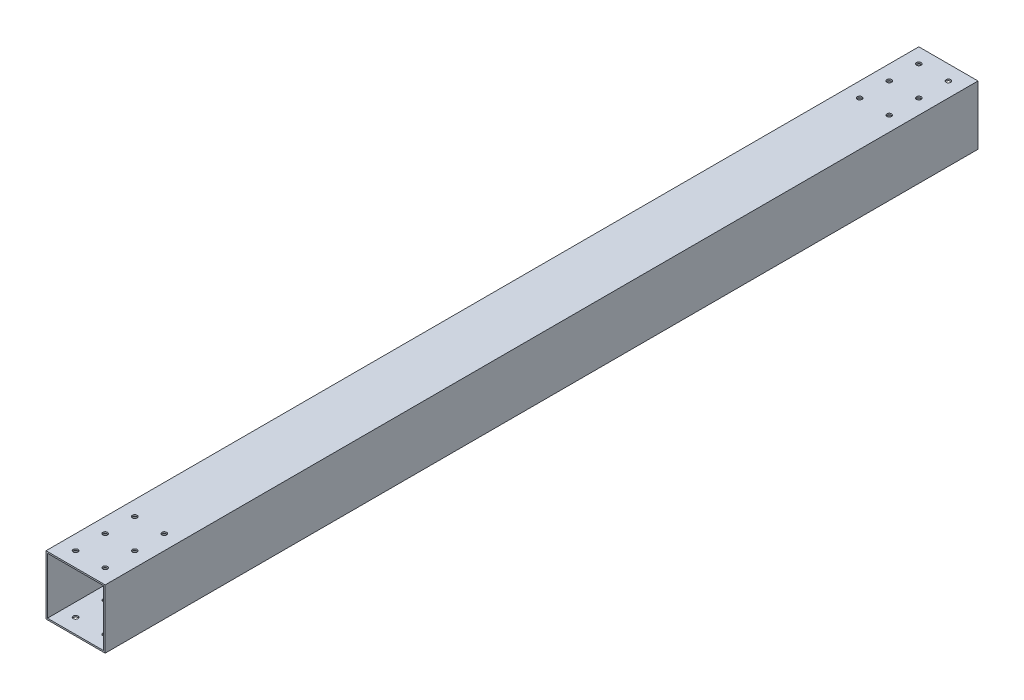
SolidWorks part; units mm, degrees
material "6061 合金"
ref_plane "前视基准面" through (0, 0, 0) normal (0, 0, 1) x (1, 0, 0)
ref_plane "上视基准面" through (0, 0, 0) normal (0, 1, 0) x (1, 0, 0)
ref_plane "右视基准面" through (0, 0, 0) normal (1, 0, 0) x (0, 0, -1)
other "Configuration Table"
sketch "草图1" plane through (0, 0, 0) normal (0, 0, 1) x (1, 0, 0)
  line L1 (-20, 20) -> (20, 20)
  line L2 (-20, 20) -> (-20, -20)
  line L3 (-20, -20) -> (20, -20)
  line L4 (20, 20) -> (20, -20)
  line L5 (-20, 20) -> (20, -20) construction
  line L6 (-20, -20) -> (20, 20) construction
  line L7 (-19, 19) -> (19, 19)
  line L8 (-19, 19) -> (-19, -19)
  line L9 (-19, -19) -> (19, -19)
  line L10 (19, 19) -> (19, -19)
  line L11 (-19, 19) -> (19, -19) construction
  line L12 (-19, -19) -> (19, 19) construction
  point P0 (0, 0)
  point P6 (0, 0)
  dimension "D1" = 40
  dimension "D2" = 1
extrude "凸台-拉伸1" add sketch "草图1" along normal mid plane 590
sketch "草图2" plane through (0, 20, 0) normal (0, 1, 0) x (1, 0, 0)
  line L0 (0, -290) -> (0, -50290) construction
  line L1 (20, -295) -> (-20, -295) construction
  line L2 (-10, -285) -> (-10, -265) construction
  line L3 (0, 0) -> (50000, 0) construction
  circle A0 centre (-10, -285) radius 1.6
  circle A1 centre (10, -285) radius 1.6
  circle A2 centre (-10, -265) radius 1.6
  circle A3 centre (10, -265) radius 1.6
  circle A4 centre (-10, -245) radius 1.6
  circle A5 centre (10, -245) radius 1.6
  circle A10 centre (10, 245) radius 1.6
  circle A11 centre (-10, 245) radius 1.6
  circle A12 centre (10, 265) radius 1.6
  circle A13 centre (-10, 265) radius 1.6
  circle A14 centre (10, 285) radius 1.6
  circle A15 centre (-10, 285) radius 1.6
  circle A16 centre (10, -225) radius 1.6 [skipped]
  circle A17 centre (-10, -225) radius 1.6 [skipped]
  point P4 (0, -295)
  dimension "D1" = 20
  dimension "D2" = 3.2
  dimension "D3" = 10
  dimension "D5" = 20
  dimension "D4" = 4
extrude "切除-拉伸1" cut sketch "草图2" against normal through all
sketch "草图3" plane through (-20, 0, 0) normal (-1, 0, 0) x (0, 0, 1)
  line L0 (-215, 10) -> (-200, 10) construction
  line L1 (-215, 17) -> (-200, 17)
  line L2 (-215, 3) -> (-200, 3)
  line L3 (295, 20) -> (-295, 20) construction
  line L4 (-295, 20) -> (-295, -20) construction
  line L5 (-95, 10) -> (-80, 10) construction
  line L6 (-95, 17) -> (-80, 17)
  line L7 (-95, 3) -> (-80, 3)
  arc A0 (-215, 17) -> (-215, 3) centre (-215, 10) ccw
  arc A1 (-200, 3) -> (-200, 17) centre (-200, 10) ccw
  arc A2 (-95, 17) -> (-95, 3) centre (-95, 10) ccw
  arc A3 (-80, 3) -> (-80, 17) centre (-80, 10) ccw
  point P2 (-207.5, 10)
  point P14 (-87.5, 10)
  dimension "D2" = 7
  dimension "D1" = 10
  dimension "D3" = 80
  dimension "D4" = 15
  dimension "D5" = 2
extrude "切除-拉伸2" cut sketch "草图3" against normal blind 10
